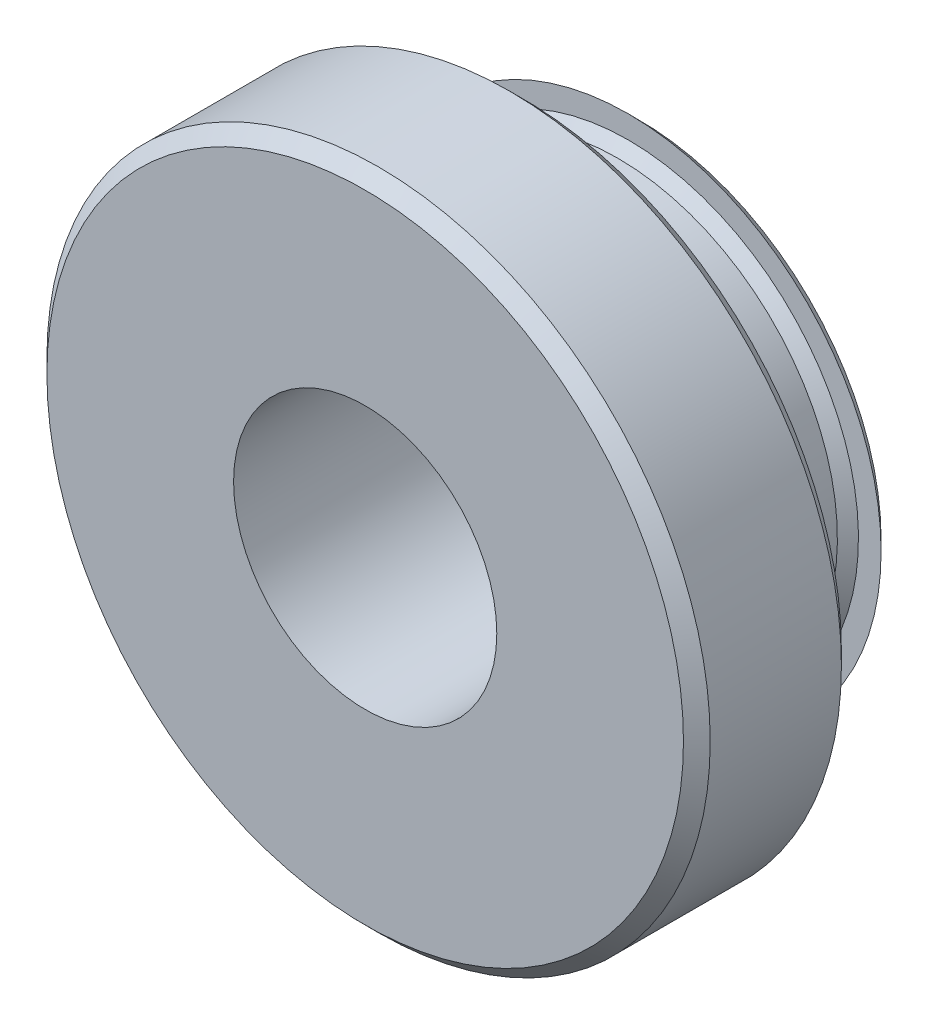
SolidWorks part; units mm, degrees
ref_plane "Front Plane" through (0, 0, 0) normal (0, 0, 1) x (1, 0, 0)
ref_plane "Top Plane" through (0, 0, 0) normal (0, 1, 0) x (1, 0, 0)
ref_plane "Right Plane" through (0, 0, 0) normal (1, 0, 0) x (0, 0, -1)
sketch "Sketch1" plane through (0, 0, 0) normal (0, 0, 1) x (1, 0, 0)
  circle A0 centre (0, 0) radius 3.15
  dimension "A" = 6.3
extrude "Extrude1" add sketch "Sketch1" against normal blind 1.5
sketch "Sketch2" plane through (0, 0, -1.5) normal (0, 0, -1) x (-1, 0, 0)
  circle A0 centre (0, 0) radius 2.2051
  dimension "D1" = 4.4102
extrude "Extrude2" add sketch "Sketch2" along normal blind 1.1
chamfer "Chamfer2" distance 0.127 angle 45 2 edges at (3.15, 0, 0) (3.15, 0, -1.5)
sketch "Эскиз2" plane through (0, 0, 0) normal (0, 0, 1) x (1, 0, 0)
  circle A0 centre (0, 0) radius 2.6
  dimension "D1" = 5.2
extrude "Бобышка-Вытянуть1" add sketch "Эскиз2" against normal up to surface (2.6 mm away) up to face at (-2.2051, 0, -2.6)
sketch "Эскиз1" plane through (0, 0, 0) normal (0, 0, 1) x (1, 0, 0)
  circle A0 centre (0, 0) radius 1.25
  dimension "D1" = 2.5
extrude "Вырез-Вытянуть1" cut sketch "Эскиз1" against normal blind 10
cosmetic thread "Условное изображение резьбы1" parameters "D2"=3
cosmetic thread "Отверстие резьбы1" parameters "D2"=3
sketch "Эскиз3" plane through (0, 0, -1.5) normal (0, 0, -1) x (-1, 0, 0)
  circle A0 centre (0, 0) radius 2.085
  circle A1 centre (0, 0) radius 2.75
  dimension "D1" = 4.17
  dimension "D2" = 5.5
extrude "Вырез-Вытянуть2" cut sketch "Эскиз3" along normal blind 1
chamfer "Фаска2" distance 0.1 angle 45 1 edges at (0, 2.085, -2.5)
chamfer "Фаска3" distance 0.3 angle 45 1 edges at (-2.6, 0, -2.6)
chamfer "Фаска4" distance 0.3 angle 45 1 edges at (-1.25, 0, -2.6)
sketch "Эскиз6" plane through (0, 0, 0) normal (0, 0, 1) x (1, 0, 0)
  circle A0 centre (0, 0) radius 1.25
extrude "Бобышка-Вытянуть2" add sketch "Эскиз6" against normal blind 3.2
hole_wizard "Отверстие обработанное метчиком M31" positions "Эскиз4" profile "Эскиз5" tap size "M3" standard "GOST" end condition through all
sketch "Эскиз4" plane through (0, 0, 0) normal (0, 0, 1) x (1, 0, 0)
  point P0 (0, 0)
sketch "Эскиз5" plane through (0, 0, 0) normal (1, 0, 0) x (0, -1, 0)
  line L0 (0, 0) -> (0, 3.2)
  line L1 (0, 3.2) -> (1.25, 3.2)
  line L2 (1.25, 3.2) -> (1.25, 0)
  line L5 (1.25, 0) -> (0, 0)
  line L11 (0, -6.35) -> (0, 107.95) construction
  dimension "Диаметр проходного сверла" = 2.5
  dimension "Глубина проходного сверла" = 3.2
cosmetic thread "Отверстие резьбы2" parameters "D2"=3
